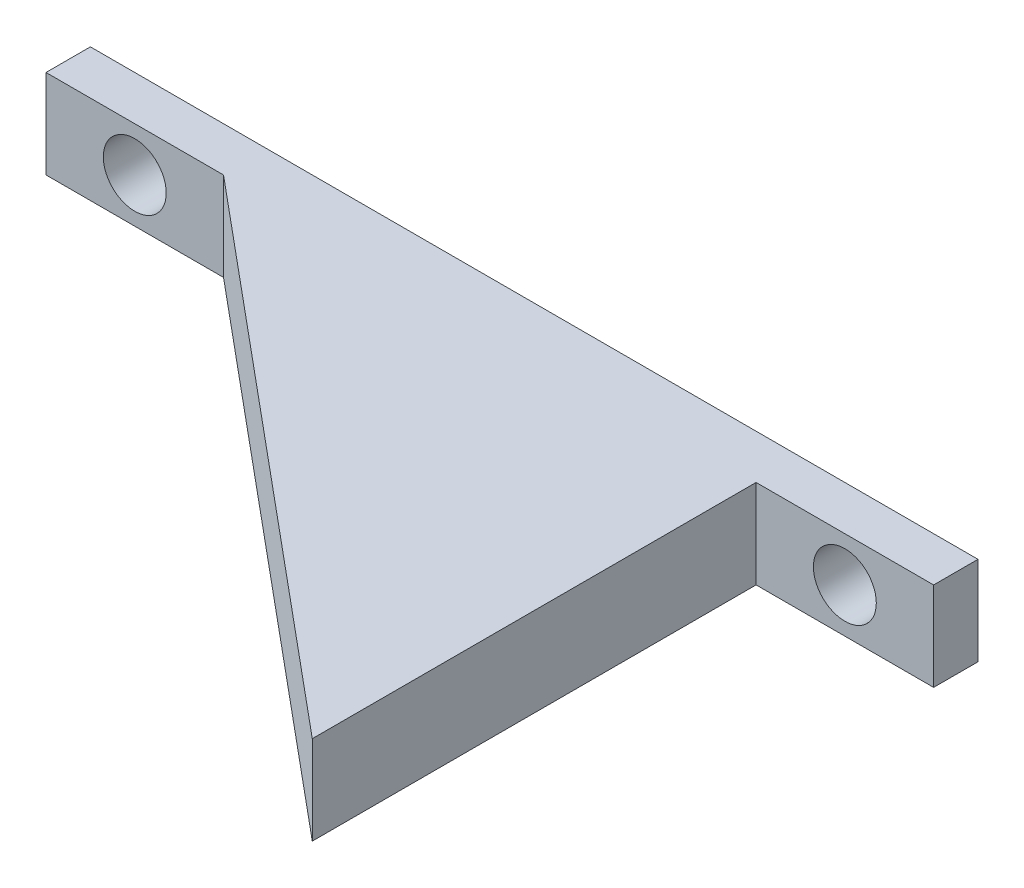
SolidWorks part; units mm, degrees
material "PLA Yellow"
ref_plane "Front" through (0, 0, 0) normal (0, 0, 1) x (1, 0, 0)
ref_plane "Top" through (0, 0, 0) normal (0, 1, 0) x (1, 0, 0)
ref_plane "Right" through (0, 0, 0) normal (1, 0, 0) x (0, 0, -1)
sketch "Sketch7" plane through (0, 0, 0) normal (0, 1, 0) x (1, 0, 0)
  line L1 (-31.75, -1.5875) -> (31.75, -1.5875)
  line L2 (-31.75, -1.5875) -> (-31.75, 1.5875)
  line L3 (-31.75, 1.5875) -> (31.75, 1.5875)
  line L4 (31.75, -1.5875) -> (31.75, 1.5875)
  line L5 (-31.75, -1.5875) -> (31.75, 1.5875) construction
  line L6 (-31.75, 1.5875) -> (31.75, -1.5875) construction
  point P0 (0, 0)
  dimension "D1" = 63.5
  dimension "D2" = 3.175
extrude "Boss-Extrude4" add sketch "Sketch7" along normal mid plane 6.35
sketch "Sketch8" plane through (0, 0, 1.5875) normal (0, 0, 1) x (1, 0, 0)
  line L0 (-25.4, 0) -> (25.4, 0) construction
  line L1 (-31.75, 3.175) -> (-31.75, -3.175) construction
  circle A0 centre (-25.4, 0) radius 2.25
  circle A1 centre (25.4, 0) radius 2.25
  point P4 (0, 0)
  dimension "D1" = 4.5
  dimension "D2" = 6.35
extrude "Cut-Extrude3" cut sketch "Sketch8" against normal through all
sketch "Sketch9" plane through (0, 3.175, 0) normal (0, 1, 0) x (1, 0, 0)
  line L0 (19.05, -1.5875) -> (19.05, -33.3375)
  line L1 (-31.75, -1.5875) -> (31.75, -1.5875) construction
  line L2 (19.05, -33.3375) -> (-19.05, -1.5875)
  line L3 (-19.05, -1.5875) -> (19.05, -1.5875)
  line L5 (31.75, -1.5875) -> (31.75, 1.5875) construction
  line L6 (-31.75, 1.5875) -> (-31.75, -1.5875) construction
  dimension "D1" = 31.75
  dimension "D2" = 12.7
  dimension "D3" = 12.7
extrude "Boss-Extrude5" add sketch "Sketch9" against normal up to surface (6.35 mm away) up to face at (0, -3.175, 0)
